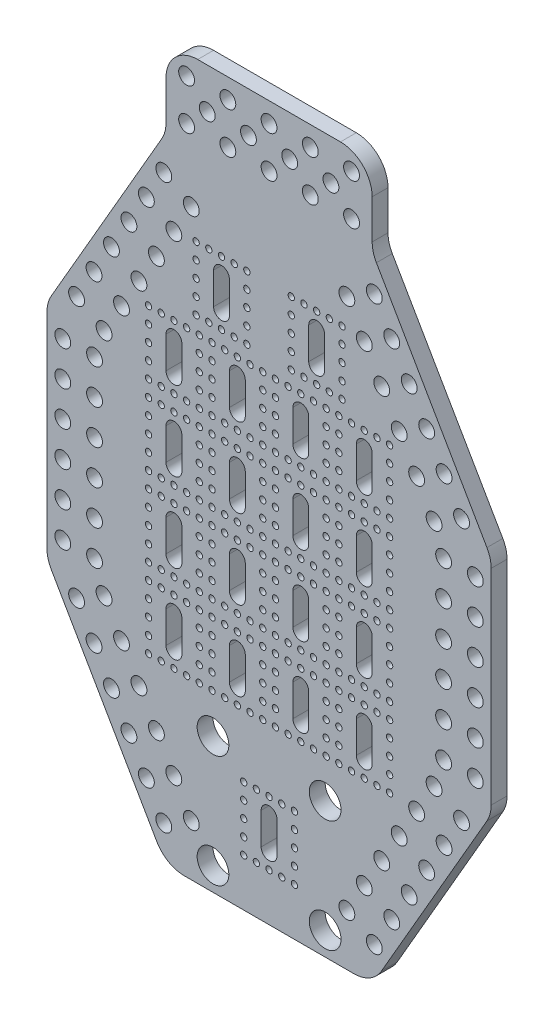
SolidWorks part; units mm, degrees
ref_plane "前视基准面" through (0, 0, 0) normal (0, 0, 1) x (1, 0, 0)
ref_plane "上视基准面" through (0, 0, 0) normal (0, 1, 0) x (1, 0, 0)
ref_plane "右视基准面" through (0, 0, 0) normal (1, 0, 0) x (0, 0, -1)
other "Configuration Table"
sketch "Sketch1" plane through (0, 0, 0) normal (0, 0, 1) x (1, 0, 0)
  line L0 (0, 0) -> (0, 100) construction
  line L1 (-32.5, -100) -> (32.5, -100)
  line L2 (-32.5, -100) -> (-32.5, 100)
  line L3 (-32.5, 100) -> (32.5, 100)
  line L4 (32.5, -100) -> (32.5, 100)
  line L5 (-32.5, -100) -> (32.5, 100) construction
  line L6 (-32.5, 100) -> (32.5, -100) construction
  line L7 (-32.5, 100) -> (-70.0278, 35)
  line L8 (-70.0278, 35) -> (-70.0278, -35)
  line L9 (0, 0) -> (-70.0278, 0) construction
  line L10 (-32.5, -100) -> (-70.0278, -35)
  line L11 (32.5, -100) -> (70.0278, -35)
  line L12 (32.5, 100) -> (70.0278, 35)
  line L13 (70.0278, 35) -> (70.0278, -35)
  point P0 (0, 0)
  dimension "D1" = 65
  dimension "D2" = 200
  dimension "D3" = 35
  dimension "D4" = 30
extrude "Boss-Extrude1" add sketch "Sketch1" along normal mid plane 5 contours L10 L2 L7 L8 | L1 L4 L3 L2 | L13 L12 L4 L11 region at (0, 0, 0) region at (-48.2524, 0, 0) region at (48.2524, 0, 0)
sketch "Sketch2" plane through (0, 0, -2.5) normal (0, 0, -1) x (-1, 0, 0)
  line L0 (0, 0) -> (0, 100) construction
  line L1 (32.5, 100) -> (-32.5, 100) construction
  line L2 (-32.5, 100) -> (-70.0278, 35) construction
  line L3 (-70.0278, 35) -> (-51.2639, 67.5) construction
  line L4 (-51.2639, 67.5) -> (-33.9434, 57.5) construction
  line L5 (-56.7639, 57.9737) -> (-45.7639, 77.0263)
  line L6 (-45.7639, 77.0263) -> (-28.4434, 67.0263)
  line L7 (-39.4434, 47.9737) -> (-28.4434, 67.0263)
  line L8 (-56.7639, 57.9737) -> (-39.4434, 47.9737)
  line L9 (-42.6036, 62.5) -> (-37.1036, 72.0263) construction
  line L10 (-37.1036, 72.0263) -> (-33.9434, 57.5) construction
  line L11 (-33.9434, 57.5) -> (-35.5235, 64.7631) construction
  line L12 (33.9434, 57.5) -> (35.5235, 64.7631) construction
  line L13 (37.1036, 72.0263) -> (33.9434, 57.5) construction
  line L14 (42.6036, 62.5) -> (37.1036, 72.0263) construction
  line L15 (51.2639, 67.5) -> (33.9434, 57.5) construction
  line L16 (70.0278, 35) -> (51.2639, 67.5) construction
  line L17 (32.5, 100) -> (70.0278, 35) construction
  line L18 (56.7639, 57.9737) -> (39.4434, 47.9737)
  line L19 (39.4434, 47.9737) -> (28.4434, 67.0263)
  line L20 (45.7639, 77.0263) -> (28.4434, 67.0263)
  line L21 (56.7639, 57.9737) -> (45.7639, 77.0263)
  line L22 (0, 0) -> (-70.0278, 0) construction
  line L23 (-70.0278, 35) -> (-70.0278, -35) construction
  line L24 (-70.0278, 0) -> (-50.0278, 0) construction
  line L25 (-70.0278, -11) -> (-70.0278, 11)
  line L26 (-70.0278, 11) -> (-50.0278, 11)
  line L27 (-50.0278, 11) -> (-50.0278, 0)
  line L28 (-50.0278, 0) -> (-70.0278, 0) construction
  line L29 (-70.0278, 0) -> (-60.0278, 0) construction
  line L30 (-60.0278, 0) -> (-60.0278, 11) construction
  line L31 (-60.0278, 11) -> (-60.0278, 5.5) construction
  line L32 (-60.0278, 5.5) -> (-50.0278, 5.5) construction
  line L33 (-50.0278, 5.5) -> (-55.0278, 5.5) construction
  line L34 (-50.0278, -5.5) -> (-55.0278, -5.5) construction
  line L35 (-60.0278, -5.5) -> (-50.0278, -5.5) construction
  line L36 (-60.0278, -11) -> (-60.0278, -5.5) construction
  line L37 (-60.0278, 0) -> (-60.0278, -11) construction
  line L38 (-50.0278, -11) -> (-50.0278, 0)
  line L39 (-70.0278, -11) -> (-50.0278, -11)
  line L40 (60.0278, 0) -> (60.0278, -11) construction
  line L41 (60.0278, -11) -> (60.0278, -5.5) construction
  line L42 (60.0278, -5.5) -> (50.0278, -5.5) construction
  line L43 (50.0278, -5.5) -> (55.0278, -5.5) construction
  line L44 (50.0278, 5.5) -> (55.0278, 5.5) construction
  line L45 (60.0278, 5.5) -> (50.0278, 5.5) construction
  line L46 (60.0278, 11) -> (60.0278, 5.5) construction
  line L47 (60.0278, 0) -> (60.0278, 11) construction
  line L48 (70.0278, 0) -> (60.0278, 0) construction
  line L49 (50.0278, 0) -> (70.0278, 0) construction
  line L50 (70.0278, 0) -> (50.0278, 0) construction
  line L51 (70.0278, -11) -> (50.0278, -11)
  line L52 (50.0278, -11) -> (50.0278, 0)
  line L53 (50.0278, 11) -> (50.0278, 0)
  line L54 (70.0278, 11) -> (50.0278, 11)
  line L55 (70.0278, -11) -> (70.0278, 11)
  line L56 (70.0278, -35) -> (51.2639, -67.5) construction
  line L57 (51.2639, -67.5) -> (33.9434, -57.5) construction
  line L58 (42.6036, -62.5) -> (37.1036, -72.0263) construction
  line L59 (37.1036, -72.0263) -> (33.9434, -57.5) construction
  line L60 (33.9434, -57.5) -> (35.5235, -64.7631) construction
  line L61 (-33.9434, -57.5) -> (-35.5235, -64.7631) construction
  line L62 (-37.1036, -72.0263) -> (-33.9434, -57.5) construction
  line L63 (-42.6036, -62.5) -> (-37.1036, -72.0263) construction
  line L64 (-51.2639, -67.5) -> (-33.9434, -57.5) construction
  line L65 (-70.0278, -35) -> (-51.2639, -67.5) construction
  line L66 (56.7639, -57.9737) -> (45.7639, -77.0263)
  line L67 (45.7639, -77.0263) -> (28.4434, -67.0263)
  line L68 (39.4434, -47.9737) -> (28.4434, -67.0263)
  line L69 (56.7639, -57.9737) -> (39.4434, -47.9737)
  line L70 (-56.7639, -57.9737) -> (-39.4434, -47.9737)
  line L71 (-39.4434, -47.9737) -> (-28.4434, -67.0263)
  line L72 (-45.7639, -77.0263) -> (-28.4434, -67.0263)
  line L73 (-56.7639, -57.9737) -> (-45.7639, -77.0263)
  line L74 (70.0278, -35) -> (51.2639, -67.5) construction
  line L75 (51.2639, -67.5) -> (33.9434, -57.5) construction
  line L76 (42.6036, -62.5) -> (37.1036, -72.0263) construction
  line L77 (37.1036, -72.0263) -> (33.9434, -57.5) construction
  line L78 (33.9434, -57.5) -> (35.5235, -64.7631) construction
  line L79 (60.0278, 0) -> (60.0278, -11) construction
  line L80 (60.0278, -11) -> (60.0278, -5.5) construction
  line L81 (60.0278, -5.5) -> (50.0278, -5.5) construction
  line L82 (50.0278, -5.5) -> (55.0278, -5.5) construction
  line L83 (50.0278, 5.5) -> (55.0278, 5.5) construction
  line L84 (60.0278, 5.5) -> (50.0278, 5.5) construction
  line L85 (60.0278, 11) -> (60.0278, 5.5) construction
  line L86 (60.0278, 0) -> (60.0278, 11) construction
  line L87 (70.0278, 0) -> (60.0278, 0) construction
  line L88 (50.0278, 0) -> (70.0278, 0) construction
  line L89 (70.0278, 0) -> (50.0278, 0) construction
  line L90 (33.9434, 57.5) -> (35.5235, 64.7631) construction
  line L91 (37.1036, 72.0263) -> (33.9434, 57.5) construction
  line L92 (42.6036, 62.5) -> (37.1036, 72.0263) construction
  line L93 (51.2639, 67.5) -> (33.9434, 57.5) construction
  line L94 (70.0278, 35) -> (51.2639, 67.5) construction
  line L95 (32.5, 100) -> (70.0278, 35) construction
  line L96 (56.7639, -57.9737) -> (45.7639, -77.0263)
  line L97 (45.7639, -77.0263) -> (28.4434, -67.0263)
  line L98 (39.4434, -47.9737) -> (28.4434, -67.0263)
  line L99 (56.7639, -57.9737) -> (39.4434, -47.9737)
  line L100 (70.0278, -11) -> (50.0278, -11)
  line L101 (50.0278, -11) -> (50.0278, 0)
  line L102 (50.0278, 11) -> (50.0278, 0)
  line L103 (70.0278, 11) -> (50.0278, 11)
  line L104 (70.0278, -11) -> (70.0278, 11)
  line L105 (56.7639, 57.9737) -> (39.4434, 47.9737)
  line L106 (39.4434, 47.9737) -> (28.4434, 67.0263)
  line L107 (45.7639, 77.0263) -> (28.4434, 67.0263)
  line L108 (56.7639, 57.9737) -> (45.7639, 77.0263)
  circle A0 centre (-35.5235, 64.7631) radius 2.5
  circle A1 centre (-44.1838, 69.7631) radius 2.5
  circle A2 centre (-41.0235, 55.2369) radius 2.5
  circle A3 centre (-49.6838, 60.2369) radius 2.5
  circle A4 centre (49.6838, 60.2369) radius 2.5
  circle A5 centre (41.0235, 55.2369) radius 2.5
  circle A6 centre (44.1838, 69.7631) radius 2.5
  circle A7 centre (35.5235, 64.7631) radius 2.5
  circle A8 centre (-55.0278, 5.5) radius 2.5
  circle A9 centre (-55.0278, -5.5) radius 2.5
  circle A10 centre (-65.0278, -5.5) radius 2.5
  circle A11 centre (-65.0278, 5.5) radius 2.5
  circle A12 centre (65.0278, 5.5) radius 2.5
  circle A13 centre (65.0278, -5.5) radius 2.5
  circle A14 centre (55.0278, -5.5) radius 2.5
  circle A15 centre (55.0278, 5.5) radius 2.5
  circle A16 centre (35.5235, -64.7631) radius 2.5
  circle A17 centre (44.1838, -69.7631) radius 2.5
  circle A18 centre (41.0235, -55.2369) radius 2.5
  circle A19 centre (49.6838, -60.2369) radius 2.5
  circle A20 centre (-49.6838, -60.2369) radius 2.5
  circle A21 centre (-41.0235, -55.2369) radius 2.5
  circle A22 centre (-44.1838, -69.7631) radius 2.5
  circle A23 centre (-35.5235, -64.7631) radius 2.5
  circle A24 centre (-24.5235, 83.8157) radius 2.5
  circle A25 centre (-30.0235, 74.2894) radius 2.5
  circle A26 centre (-38.6838, 79.2894) radius 2.5
  circle A27 centre (-33.1838, 88.8157) radius 2.5
  circle A28 centre (-55.1838, 50.7106) radius 2.5
  circle A29 centre (-46.5235, 45.7106) radius 2.5
  circle A30 centre (-52.0235, 36.1843) radius 2.5
  circle A31 centre (-60.6838, 41.1843) radius 2.5
  circle A32 centre (-55.0278, 27.5) radius 2.5
  circle A33 centre (-65.0278, 27.5) radius 2.5
  circle A34 centre (-55.0278, 16.5) radius 2.5
  circle A35 centre (-65.0278, 16.5) radius 2.5
  circle A36 centre (-55.0278, -16.5) radius 2.5
  circle A37 centre (-65.0278, -16.5) radius 2.5
  circle A38 centre (-55.0278, -27.5) radius 2.5
  circle A39 centre (-65.0278, -27.5) radius 2.5
  circle A40 centre (-52.0235, -36.1843) radius 2.5
  circle A41 centre (-60.6838, -41.1843) radius 2.5
  circle A42 centre (-46.5235, -45.7106) radius 2.5
  circle A43 centre (-55.1838, -50.7106) radius 2.5
  circle A44 centre (-30.0235, -74.2894) radius 2.5
  circle A45 centre (-24.5235, -83.8157) radius 2.5
  circle A46 centre (-38.6838, -79.2894) radius 2.5
  circle A47 centre (-33.1838, -88.8157) radius 2.5
  circle A48 centre (33.1838, -88.8157) radius 2.5
  circle A49 centre (38.6838, -79.2894) radius 2.5
  circle A50 centre (24.5235, -83.8157) radius 2.5
  circle A51 centre (30.0235, -74.2894) radius 2.5
  circle A52 centre (55.1838, -50.7106) radius 2.5
  circle A53 centre (46.5235, -45.7106) radius 2.5
  circle A54 centre (60.6838, -41.1843) radius 2.5
  circle A55 centre (52.0235, -36.1843) radius 2.5
  circle A56 centre (65.0278, -27.5) radius 2.5
  circle A57 centre (55.0278, -27.5) radius 2.5
  circle A58 centre (65.0278, -16.5) radius 2.5
  circle A59 centre (55.0278, -16.5) radius 2.5
  circle A60 centre (65.0278, 16.5) radius 2.5
  circle A61 centre (55.0278, 16.5) radius 2.5
  circle A62 centre (65.0278, 27.5) radius 2.5
  circle A63 centre (55.0278, 27.5) radius 2.5
  circle A64 centre (60.6838, 41.1843) radius 2.5
  circle A65 centre (52.0235, 36.1843) radius 2.5
  circle A66 centre (46.5235, 45.7106) radius 2.5
  circle A67 centre (55.1838, 50.7106) radius 2.5
  circle A68 centre (33.1838, 88.8157) radius 2.5
  circle A69 centre (38.6838, 79.2894) radius 2.5
  circle A70 centre (30.0235, 74.2894) radius 2.5
  circle A71 centre (24.5235, 83.8157) radius 2.5
  circle A72 centre (35.5235, -64.7631) radius 2.5
  circle A73 centre (44.1838, -69.7631) radius 2.5
  circle A74 centre (41.0235, -55.2369) radius 2.5
  circle A75 centre (49.6838, -60.2369) radius 2.5
  circle A76 centre (65.0278, 5.5) radius 2.5
  circle A77 centre (65.0278, -5.5) radius 2.5
  circle A78 centre (55.0278, -5.5) radius 2.5
  circle A79 centre (55.0278, 5.5) radius 2.5
  circle A80 centre (49.6838, 60.2369) radius 2.5
  circle A81 centre (41.0235, 55.2369) radius 2.5
  circle A82 centre (44.1838, 69.7631) radius 2.5
  circle A83 centre (35.5235, 64.7631) radius 2.5
  dimension "D3" = 5
  dimension "D6" = 5
  dimension "D1" = 22
  dimension "D2" = 20
  dimension "D4" = 20
  dimension "D5" = 22
sketch "Sketch3" plane through (0, 0, -2.5) normal (0, 0, -1) x (-1, 0, 0)
  line L0 (0, 0) -> (0, -75) construction
  line L1 (0, -50) -> (0, -75) construction
  line L2 (-25, -100) -> (25, -100)
  line L3 (-25, -100) -> (-25, -50)
  line L4 (-25, -50) -> (25, -50)
  line L5 (25, -100) -> (25, -50)
  line L6 (-25, -100) -> (25, -50) construction
  line L7 (-25, -50) -> (25, -100) construction
  line L8 (0, -75) -> (25, -75) construction
  line L9 (25, -75) -> (12.5, -75) construction
  line L10 (0, -75) -> (17.6777, -57.3223) construction
  circle A4 centre (17.6777, -57.3223) radius 5
  circle A5 centre (-17.6777, -57.3223) radius 5
  circle A6 centre (17.6777, -92.6777) radius 5
  circle A7 centre (-17.6777, -92.6777) radius 5
  dimension "D3" = 10
  dimension "D1" = 50
  dimension "D2" = 75
  dimension "D4" = 25
sketch "Sketch5" plane through (0, 0, -2.5) normal (0, 0, -1) x (-1, 0, 0)
  line L0 (0, 0) -> (0, 40) construction
  line L1 (0, 40) -> (30, 40) construction
  line L2 (30, 40) -> (38, 40) construction
  line L3 (27.5, 35) -> (32.5, 35)
  line L4 (27.5, 35) -> (27.5, 45)
  line L5 (27.5, 45) -> (32.5, 45)
  line L6 (32.5, 35) -> (32.5, 45)
  line L7 (27.5, 35) -> (32.5, 45) construction
  line L8 (27.5, 45) -> (32.5, 35) construction
  line L9 (38, 40) -> (38, 50) construction
  line L10 (38, 50) -> (38, 45) construction
  line L11 (30, 40) -> (30, 45) construction
  line L12 (22, 50) -> (22, 45) construction
  line L13 (22, 40) -> (22, 50) construction
  line L14 (22, 50) -> (38, 50) construction
  line L15 (38, 50) -> (30, 50) construction
  line L16 (30, 50) -> (34, 50) construction
  circle A0 centre (30, 45) radius 2.5
  circle A1 centre (30, 35) radius 2.5
  circle A2 centre (38, 50) radius 1
  circle A3 centre (38, 45) radius 1
  circle A4 centre (38, 40) radius 1
  circle A5 centre (38, 35) radius 1
  circle A6 centre (38, 30) radius 1
  circle A7 centre (22, 30) radius 1
  circle A8 centre (22, 35) radius 1
  circle A9 centre (22, 40) radius 1
  circle A10 centre (22, 45) radius 1
  circle A11 centre (22, 50) radius 1
  circle A12 centre (34, 50) radius 1
  circle A13 centre (30, 50) radius 1
  circle A14 centre (26, 50) radius 1
  circle A15 centre (34, 30) radius 1
  circle A16 centre (30, 30) radius 1
  circle A17 centre (26, 30) radius 1
  dimension "D3" = 2
  dimension "D4" = 2
  dimension "D5" = 2
  dimension "D10" = 2
  dimension "D11" = 2
  dimension "D1" = 10
  dimension "D2" = 5
  dimension "D6" = 8
  dimension "D7" = 5
  dimension "D8" = 30
  dimension "D9" = 40
extrude "Cut-Extrude2" cut sketch "Sketch5" against normal blind 5 contours A1 L6 A0 L4 | L5 A0 | A9 | A8 | L3 A1 | L3 A1 | A5 | A3 | A2 | A6 | A14 | A13 | A12 | A15 | A16 | A17 | A0 | A11 | A7 | A4 | A10 region at (-30, 36.061, -2.5) region at (-30, 40, -2.5) region at (-30, 33.939, -2.5) region at (-30, 46.061, -2.5) region at (-38, 50, -2.5) region at (-38, 45, -2.5) region at (-38, 35, -2.5) region at (-38, 30, -2.5) region at (-22, 35, -2.5) region at (-22, 40, -2.5) region at (-34, 50, -2.5) region at (-30, 50, -2.5) region at (-26, 50, -2.5) region at (-34, 30, -2.5) region at (-30, 30, -2.5) region at (-26, 30, -2.5)
pattern_linear "LPattern1" count 4 spacing 20 along (1, 0, 0) of "Cut-Extrude2"
pattern_linear "LPattern2" count 4 spacing 25 along (0, -1, 0) of "LPattern1"
sketch "Sketch9" plane through (0, 0, -2.5) normal (0, 0, -1) x (-1, 0, 0)
  line L0 (-32.5, 100) -> (-32.5, 125)
  line L1 (-32.5, 125) -> (32.5, 125)
  line L2 (32.5, 125) -> (32.5, 100)
  line L3 (-32.5, 100) -> (32.5, 100)
  dimension "D1" = 25
extrude "Boss-Extrude6" add sketch "Sketch9" against normal blind 5
extrude "Cut-Extrude3" cut sketch "Sketch2" against normal blind 5 contours A1 | A3 | A2 | A0 | A11 | A8 | A9 | A10 | A20 | A21 | A23 | A22 | A19 | A17 | A18 | A14 | A15 | A12 | A7 | A4 | A5 | A27 | A25 | A26 | A28 | A31 | A33 | A35 | A34 | A29 | A42 | A43 | A41 | A40 | A38 | A37 | A36 | A46 | A47 | A45 | A44 | A50 | A57 | A52 | A48 | A62 | A68 | A70 | A69 | A66 | A67 | A65 | A64 | A16 | A13 | A6 | A5 | A24 | A32 | A30 | A39 | A51 | A49 | A54 | A53 | A55 | A59 | A58 | A56 | A63 | A61 | A60 | A71 region at (35.5235, 64.7631, -2.5) region at (44.1838, 69.7631, -2.5) region at (41.0235, 55.2369, -2.5) region at (49.6838, 60.2369, -2.5) region at (-49.6838, 60.2369, -2.5) region at (-41.0235, 55.2369, -2.5) region at (-35.5235, 64.7631, -2.5) region at (55.0278, 5.5, -2.5) region at (55.0278, -5.5, -2.5) region at (65.0278, -5.5, -2.5) region at (65.0278, 5.5, -2.5) region at (-65.0278, 5.5, -2.5) region at (-55.0278, -5.5, -2.5) region at (-55.0278, 5.5, -2.5) region at (-44.1838, -69.7631, -2.5) region at (-41.0235, -55.2369, -2.5) region at (-49.6838, -60.2369, -2.5) region at (49.6838, -60.2369, -2.5) region at (41.0235, -55.2369, -2.5) region at (44.1838, -69.7631, -2.5) region at (35.5235, -64.7631, -2.5) region at (30.0235, 74.2894, -2.5) region at (38.6838, 79.2894, -2.5) region at (33.1838, 88.8157, -2.5) region at (55.1838, 50.7106, -2.5) region at (46.5235, 45.7106, -2.5) region at (60.6838, 41.1843, -2.5) region at (65.0278, 27.5, -2.5) region at (55.0278, 16.5, -2.5) region at (65.0278, 16.5, -2.5) region at (55.0278, -16.5, -2.5) region at (65.0278, -16.5, -2.5) region at (55.0278, -27.5, -2.5) region at (52.0235, -36.1843, -2.5) region at (60.6838, -41.1843, -2.5) region at (46.5235, -45.7106, -2.5) region at (55.1838, -50.7106, -2.5) region at (30.0235, -74.2894, -2.5) region at (24.5235, -83.8157, -2.5) region at (38.6838, -79.2894, -2.5) region at (33.1838, -88.8157, -2.5) region at (-33.1838, -88.8157, -2.5) region at (-24.5235, -83.8157, -2.5) region at (-55.1838, -50.7106, -2.5) region at (-55.0278, -27.5, -2.5) region at (-65.0278, 27.5, -2.5) region at (-60.6838, 41.1843, -2.5) region at (-52.0235, 36.1843, -2.5) region at (-46.5235, 45.7106, -2.5) region at (-55.1838, 50.7106, -2.5) region at (-33.1838, 88.8157, -2.5) region at (-38.6838, 79.2894, -2.5) region at (-30.0235, 74.2894, -2.5)
sketch "Sketch12" plane through (0, 0, -2.5) normal (0, 0, -1) x (-1, 0, 0)
  line L0 (-32.5, 125) -> (-32.5, 100) construction
  line L1 (-32.5, 125) -> (-32.5, 100) construction
  line L2 (-32.5, 100) -> (-32.5, 112.5) construction
  line L4 (-32.5, 112.5) -> (-32.5, 125) construction
  line L5 (-32.5, 125) -> (-32.5, 118.75) construction
  line L6 (-32.5, 118.75) -> (-26, 118.75) construction
  line L9 (-26, 118.75) -> (-13, 105.75) construction
  line L10 (-13, 105.75) -> (0, 118.75) construction
  line L11 (0, 118.75) -> (13, 105.75) construction
  line L12 (13, 105.75) -> (26, 118.75) construction
  line L13 (26, 118.75) -> (19.5, 112.25) construction
  circle A23 centre (-26, 118.75) radius 2.5
  circle A24 centre (-26, 105.75) radius 2.5
  circle A25 centre (-13, 118.75) radius 2.5
  circle A26 centre (-13, 105.75) radius 2.5
  circle A27 centre (0, 118.75) radius 2.5
  circle A28 centre (0, 105.75) radius 2.5
  circle A29 centre (13, 118.75) radius 2.5
  circle A30 centre (13, 105.75) radius 2.5
  circle A31 centre (26, 118.75) radius 2.5
  circle A32 centre (26, 105.75) radius 2.5
  circle A33 centre (-19.5, 112.25) radius 2.5
  circle A34 centre (-6.5, 112.25) radius 2.5
  circle A35 centre (6.5, 112.25) radius 2.5
  circle A36 centre (19.5, 112.25) radius 2.5
  dimension "D1" = 5
  dimension "D2" = 6.5
  dimension "D4" = 5
  dimension "D3" = 2
  dimension "D5" = 13
sketch "Sketch13" plane through (0, 0, -2.5) normal (0, 0, -1) x (-1, 0, 0)
  line L0 (0, 0) -> (0, 65) construction
  line L1 (0, 65) -> (15, 65) construction
  line L2 (-15, 75) -> (-19, 75) construction
  line L3 (15, 65) -> (23, 65) construction
  line L4 (12.5, 60) -> (17.5, 60)
  line L5 (12.5, 60) -> (12.5, 70)
  line L6 (12.5, 70) -> (17.5, 70)
  line L7 (17.5, 60) -> (17.5, 70)
  line L8 (12.5, 60) -> (17.5, 70) construction
  line L9 (12.5, 70) -> (17.5, 60) construction
  line L10 (23, 65) -> (23, 75) construction
  line L11 (23, 75) -> (23, 70) construction
  line L12 (15, 65) -> (15, 70) construction
  line L13 (7, 75) -> (7, 70) construction
  line L14 (7, 65) -> (7, 75) construction
  line L15 (7, 75) -> (23, 75) construction
  line L16 (23, 75) -> (15, 75) construction
  line L17 (15, 75) -> (19, 75) construction
  line L18 (-23, 75) -> (-15, 75) construction
  line L19 (-7, 75) -> (-23, 75) construction
  line L20 (-7, 65) -> (-7, 75) construction
  line L21 (-7, 75) -> (-7, 70) construction
  line L22 (-15, 65) -> (-15, 70) construction
  line L23 (-23, 75) -> (-23, 70) construction
  line L24 (-23, 65) -> (-23, 75) construction
  line L25 (-12.5, 70) -> (-17.5, 60) construction
  line L26 (-12.5, 60) -> (-17.5, 70) construction
  line L27 (-15, 65) -> (-23, 65) construction
  line L28 (-17.5, 60) -> (-17.5, 70)
  line L29 (-12.5, 70) -> (-17.5, 70)
  line L30 (-12.5, 60) -> (-12.5, 70)
  line L31 (-12.5, 60) -> (-17.5, 60)
  circle A0 centre (15, 70) radius 2.5
  circle A1 centre (15, 60) radius 2.5
  circle A2 centre (23, 75) radius 1
  circle A3 centre (23, 70) radius 1
  circle A4 centre (23, 65) radius 1
  circle A5 centre (23, 60) radius 1
  circle A6 centre (23, 55) radius 1
  circle A7 centre (7, 55) radius 1
  circle A8 centre (7, 60) radius 1
  circle A9 centre (7, 65) radius 1
  circle A10 centre (7, 70) radius 1
  circle A11 centre (7, 75) radius 1
  circle A12 centre (19, 75) radius 1
  circle A13 centre (15, 75) radius 1
  circle A14 centre (11, 75) radius 1
  circle A15 centre (19, 55) radius 1
  circle A16 centre (15, 55) radius 1
  circle A17 centre (11, 55) radius 1
  circle A18 centre (-11, 55) radius 1
  circle A19 centre (-15, 55) radius 1
  circle A20 centre (-19, 55) radius 1
  circle A21 centre (-11, 75) radius 1
  circle A22 centre (-15, 75) radius 1
  circle A23 centre (-19, 75) radius 1
  circle A24 centre (-7, 75) radius 1
  circle A25 centre (-7, 70) radius 1
  circle A26 centre (-7, 65) radius 1
  circle A27 centre (-7, 60) radius 1
  circle A28 centre (-7, 55) radius 1
  circle A29 centre (-23, 55) radius 1
  circle A30 centre (-23, 60) radius 1
  circle A31 centre (-23, 65) radius 1
  circle A32 centre (-23, 70) radius 1
  circle A33 centre (-23, 75) radius 1
  circle A34 centre (-15, 60) radius 2.5
  circle A35 centre (-15, 70) radius 2.5
  dimension "D3" = 2
  dimension "D4" = 2
  dimension "D5" = 2
  dimension "D9" = 2
  dimension "D10" = 2
  dimension "D1" = 10
  dimension "D2" = 5
  dimension "D6" = 8
  dimension "D7" = 5
  dimension "D8" = 65
  dimension "D11" = 15
extrude "Cut-Extrude5" cut sketch "Sketch13" against normal blind 5 contours A35 L29 | A35 L29 | L30 A35 L28 A34 | A34 L31 | A34 L31 | A33 | A23 | A22 | A21 | A24 | A25 | A32 | A31 | A19 | A18 | A14 | L6 A0 | L6 A0 | A1 L7 A0 L5 | L4 A1 | A5 | A4 | L4 A1 | A16 | A6 | A30 | A29 | A20 | A28 | A27 | A26 | A10 | A11 | A13 | A12 | A2 | A3 | A8 | A7 | A17 | A15 | A9 region at (-15, 61.061, -2.5) region at (-15, 65, -2.5) region at (-15, 58.939, -2.5) region at (-15, 71.061, -2.5) region at (-15, 68.939, -2.5) region at (15, 61.061, -2.5) region at (15, 65, -2.5) region at (15, 58.939, -2.5) region at (15, 71.061, -2.5) region at (15, 68.939, -2.5) region at (-23, 65, -2.5) region at (-23, 60, -2.5) region at (-23, 55, -2.5) region at (-11, 75, -2.5) region at (-15, 55, -2.5) region at (11, 55, -2.5) region at (15, 55, -2.5) region at (11, 75, -2.5) region at (15, 75, -2.5) region at (19, 75, -2.5) region at (7, 75, -2.5) region at (7, 70, -2.5) region at (23, 65, -2.5) region at (23, 70, -2.5) region at (23, 75, -2.5)
fillet "Fillet4" radius 10 10 edges at (70.0278, -35, 0) (-32.5, -100, 0) (32.5, -100, 0) (-70.0278, -35, 0) (-70.0278, 35, 0) (70.0278, 35, 0) (32.5, 100, 0) (-32.5, 100, 0) (-32.5, 125, 0) (32.5, 125, 0)
extrude "Cut-Extrude6" cut sketch "Sketch3" against normal blind 5 contours A4 | A5 | A7 | A6 region at (-17.6777, -57.3223, -2.5) region at (17.6777, -57.3223, -2.5) region at (-17.6777, -92.6777, -2.5) region at (17.6777, -92.6777, -2.5)
sketch "Sketch14" plane through (0, 0, -2.5) normal (0, 0, -1) x (-1, 0, 0)
  line L0 (0, -75) -> (8, -75) construction
  line L1 (-2.5, -80) -> (2.5, -80)
  line L2 (-2.5, -80) -> (-2.5, -70)
  line L3 (-2.5, -70) -> (2.5, -70)
  line L4 (2.5, -80) -> (2.5, -70)
  line L5 (-2.5, -80) -> (2.5, -70) construction
  line L6 (-2.5, -70) -> (2.5, -80) construction
  line L7 (8, -75) -> (8, -65) construction
  line L8 (8, -65) -> (8, -70) construction
  line L9 (0, -75) -> (0, -70) construction
  line L10 (-8, -65) -> (-8, -70) construction
  line L11 (-8, -75) -> (-8, -65) construction
  line L12 (-8, -65) -> (8, -65) construction
  line L13 (8, -65) -> (0, -65) construction
  line L14 (0, -65) -> (4, -65) construction
  line L15 (0, 0) -> (0, -75) construction
  line L16 (8, -85) -> (-8, -85) construction
  circle A0 centre (0, -70) radius 2.5
  circle A1 centre (0, -80) radius 2.5
  circle A2 centre (8, -65) radius 1
  circle A3 centre (8, -70) radius 1
  circle A4 centre (8, -75) radius 1
  circle A5 centre (8, -80) radius 1
  circle A6 centre (8, -85) radius 1
  circle A7 centre (-8, -85) radius 1
  circle A8 centre (-8, -80) radius 1
  circle A9 centre (-8, -75) radius 1
  circle A10 centre (-8, -70) radius 1
  circle A11 centre (-8, -65) radius 1
  circle A12 centre (4, -65) radius 1
  circle A13 centre (0, -65) radius 1
  circle A14 centre (-4, -65) radius 1
  circle A15 centre (4, -85) radius 1
  circle A16 centre (0, -85) radius 1
  circle A17 centre (-4, -85) radius 1
  dimension "D3" = 2
  dimension "D4" = 2
  dimension "D5" = 2
  dimension "D8" = 2
  dimension "D9" = 2
  dimension "D1" = 10
  dimension "D2" = 5
  dimension "D6" = 8
  dimension "D7" = 5
  dimension "D10" = 75
extrude "Cut-Extrude7" cut sketch "Sketch14" against normal blind 5 contours L1 A1 | L1 A1 | A1 L4 A0 L2 | L3 A0 | L3 A0 | A4 | A5 | A6 | A15 | A16 | A17 | A7 | A8 | A9 | A10 | A11 | A12 | A2 | A3 | A14 | A13 region at (0, -78.939, -2.5) region at (0, -75, -2.5) region at (0, -81.061, -2.5) region at (0, -68.939, -2.5) region at (0, -71.061, -2.5) region at (-8, -65, -2.5) region at (-8, -70, -2.5) region at (-8, -75, -2.5) region at (-8, -80, -2.5) region at (-8, -85, -2.5) region at (8, -85, -2.5) region at (8, -80, -2.5) region at (8, -75, -2.5) region at (8, -70, -2.5) region at (8, -65, -2.5) region at (-4, -65, -2.5) region at (-4, -85, -2.5) region at (0, -85, -2.5) region at (4, -85, -2.5)
extrude "Cut-Extrude8" cut sketch "Sketch12" against normal blind 5
